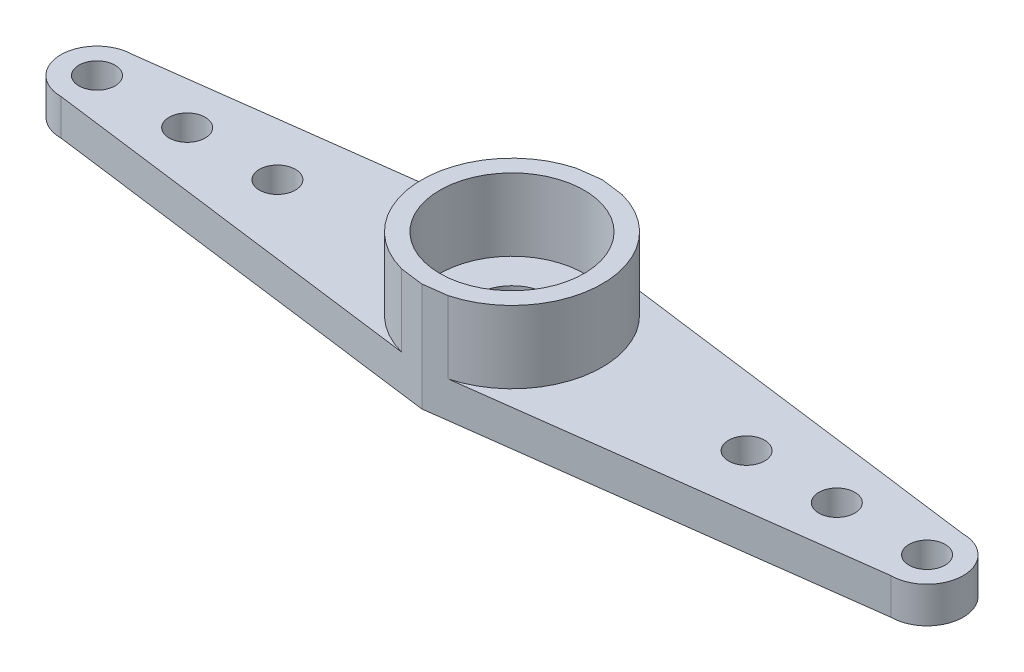
SolidWorks part; units mm, degrees
ref_plane "Front Plane" through (0, 0, 0) normal (0, 0, 1) x (1, 0, 0)
ref_plane "Top Plane" through (0, 0, 0) normal (0, 1, 0) x (1, 0, 0)
ref_plane "Right Plane" through (0, 0, 0) normal (1, 0, 0) x (0, 0, -1)
sketch "Sketch1" plane through (0, 0, 0) normal (0, 1, 0) x (1, 0, 0)
  line L0 (0, 0) -> (11.5, 0) construction
  line L1 (0, 0) -> (6.5, 0) construction
  line L2 (6.5, 0) -> (9, 0) construction
  line L3 (11.5, 1) -> (0, 2.5)
  line L4 (0, -2.5) -> (11.5, -1)
  line L5 (-11.5, -1) -> (0, -2.5)
  line L6 (0, 2.5) -> (-11.5, 1)
  circle A0 centre (0, 0) radius 2.5
  circle A1 centre (0, 0) radius 2
  circle A2 centre (0, 0) radius 1
  circle A3 centre (11.5, 0) radius 1
  circle A4 centre (11.5, 0) radius 0.5
  circle A5 centre (9, 0) radius 0.5
  circle A6 centre (6.5, 0) radius 0.5
  circle A7 centre (-6.5, 0) radius 0.5
  circle A8 centre (-9, 0) radius 0.5
  circle A9 centre (-11.5, 0) radius 1
  circle A10 centre (-11.5, 0) radius 0.5
  point P30 (0, 0)
  dimension "D1" = 2
  dimension "D2" = 11.5
extrude "Boss-Extrude1" add sketch "Sketch1" along normal blind 1 contours A9 L5 A0 L6 A7 A8 | L4 A0 L3 L6 L5 A1 | A1 A2 | A3 L3 A0 L4 A6 A5 | A3 A4 | A9 A10 region at (5.8, 0, 0) region at (12.1871, 0, -0.6871) region at (1.9255, 0, -1.4812) region at (-5.8, 0, 0) region at (-10.8129, 0, -0.6871) region at (-1.9434, 0, 0)
extrude "Boss-Extrude2" add sketch "Sketch1<4>" along normal blind 3 contours L4 A0 L3 L6 L5 A1 region at (1.9255, 0, -1.4812)
sketch "Sketch1<4>" plane through (0, 0, 0) normal (0, 1, 0) x (1, 0, 0) same geometry as "Sketch1"
